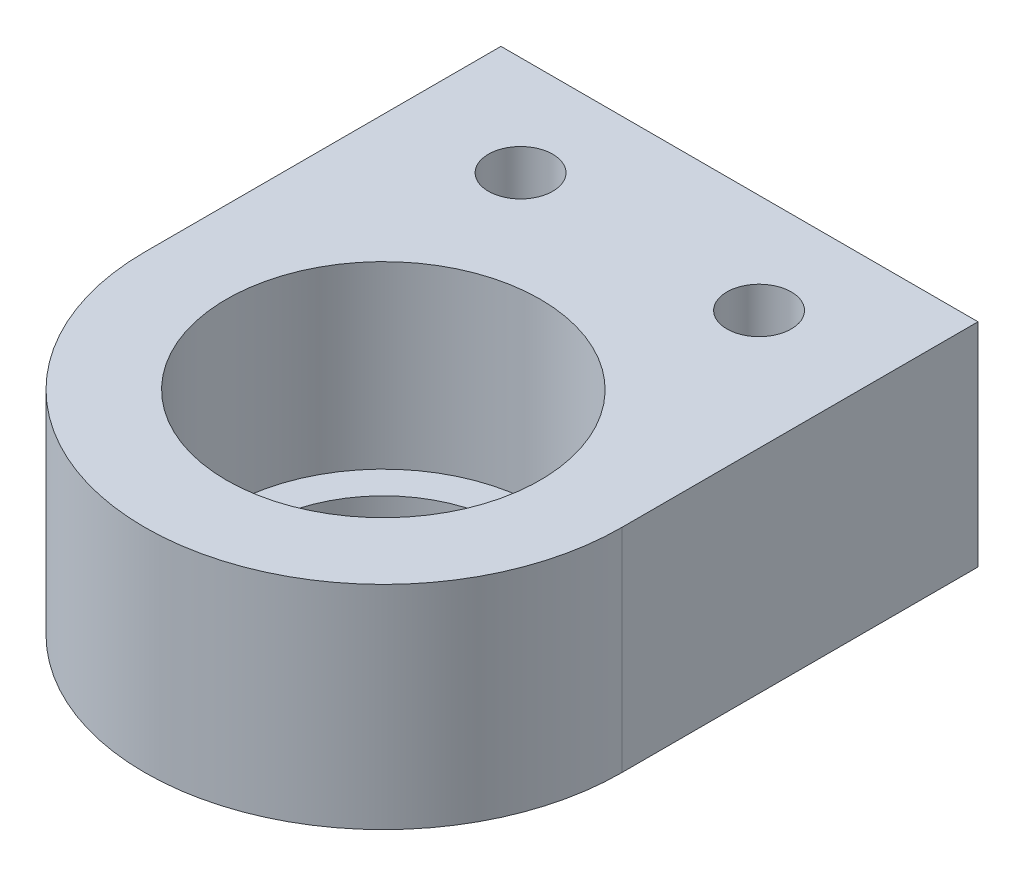
SolidWorks part; units mm, degrees
ref_plane "Front Plane" through (0, 0, 0) normal (0, 0, 1) x (1, 0, 0)
ref_plane "Top Plane" through (0, 0, 0) normal (0, 1, 0) x (1, 0, 0)
ref_plane "Right Plane" through (0, 0, 0) normal (1, 0, 0) x (0, 0, -1)
sketch "Sketch1" plane through (0, 0, 0) normal (0, 1, 0) x (1, 0, 0)
  line L0 (0, 0) -> (14.2506, 0) construction
  line L1 (0, 0) -> (0, 17.6258) construction
  line L3 (-6.096, 0) -> (-6.096, 13.843) construction
  line L4 (-9.271, 0) -> (-9.271, 10.668)
  line L5 (-9.271, 10.668) -> (-18.796, 10.668)
  line L6 (-6.096, 13.843) -> (-18.796, 13.843)
  line L7 (-18.796, 10.668) -> (-18.796, 13.843)
  line L9 (-6.096, 13.843) -> (6.096, 13.843)
  line L11 (9.271, 0) -> (9.271, 10.668)
  line L12 (18.796, 10.668) -> (18.796, 13.843)
  line L13 (6.096, 13.843) -> (18.796, 13.843)
  line L14 (9.271, 10.668) -> (18.796, 10.668)
  line L17 (-6.096, 6.9215) -> (-6.096, 10.668) construction
  line L18 (6.096, 6.9215) -> (6.096, 10.668) construction
  line L19 (-6.096, 10.668) -> (6.096, 10.668) construction
  circle A0 centre (0, 0) radius 6.096
  circle A1 centre (0, 0) radius 9.271 construction
  arc A3 (9.271, 0) -> (-9.271, 0) centre (0, 0) cw
  arc A5 (-6.096, 6.9215) -> (6.096, 6.9215) centre (0, 0) cw construction
  point P18 (0, 13.843)
  point P19 (0, 10.668)
  dimension "D1" = 12.192
  dimension "D2" = 3.175
  dimension "D3" = 13.843
  dimension "D4" = 3.175
  dimension "D5" = 12.7
extrude "Boss-Extrude1" add sketch "Sketch1" along normal blind 6.985
sketch "Sketch5" plane through (0, 0, 0) normal (0, -1, 0) x (1, 0, 0)
  line L0 (-9.271, 0) -> (-9.271, -10.668)
  line L6 (9.271, -10.668) -> (9.271, 0)
  line L7 (-9.271, -10.668) -> (-9.271, -13.843)
  line L9 (18.796, -13.843) -> (-18.796, -13.843) construction
  line L10 (-9.271, -13.843) -> (9.271, -13.843)
  line L12 (9.271, -10.668) -> (9.271, -13.843)
  circle A1 centre (0, 0) radius 6.096 construction
  circle A2 centre (0, 0) radius 9.271 construction
  circle A3 centre (0, 0) radius 4.826
  arc A4 (9.271, 0) -> (-9.271, 0) centre (0, 0) ccw
  dimension "D1" = 12.192
  dimension "D2" = 3.175
  dimension "D3" = 1.27
extrude "Boss-Extrude4" add sketch "Sketch5" along normal blind 1.27
sketch "Sketch6" plane through (0, 6.985, 0) normal (0, 1, 0) x (1, 0, 0)
  line L0 (0, 13.843) -> (0, 6.096) construction
  line L1 (18.796, 13.843) -> (-18.796, 13.843) construction
  line L2 (0, 9.9695) -> (9.271, 9.9695) construction
  line L3 (9.271, 0) -> (9.271, 10.668) construction
  circle A0 centre (0, 0) radius 6.096 construction
  circle A1 centre (4.6355, 9.9695) radius 1.25
  circle A2 centre (-4.6355, 9.9695) radius 1.25
  dimension "D1" = 2.5
extrude "Cut-Extrude2" cut sketch "Sketch6" against normal through all
sketch "Sketch7" plane through (0, 0, -10.668) normal (0, 0, 1) x (1, 0, 0)
  line L1 (9.271, 0) -> (18.796, 0)
  line L2 (9.271, 0) -> (9.271, 6.985)
  line L3 (9.271, 6.985) -> (18.796, 6.985)
  line L4 (18.796, 0) -> (18.796, 6.985)
  line L5 (-9.271, 0) -> (-18.796, 0)
  line L6 (-9.271, 0) -> (-9.271, 6.985)
  line L7 (-9.271, 6.985) -> (-18.796, 6.985)
  line L8 (-18.796, 0) -> (-18.796, 6.985)
extrude "Cut-Extrude3" cut sketch "Sketch7" against normal up to surface (3.175 mm away) up to face at (0, 1.4288, -13.843)
